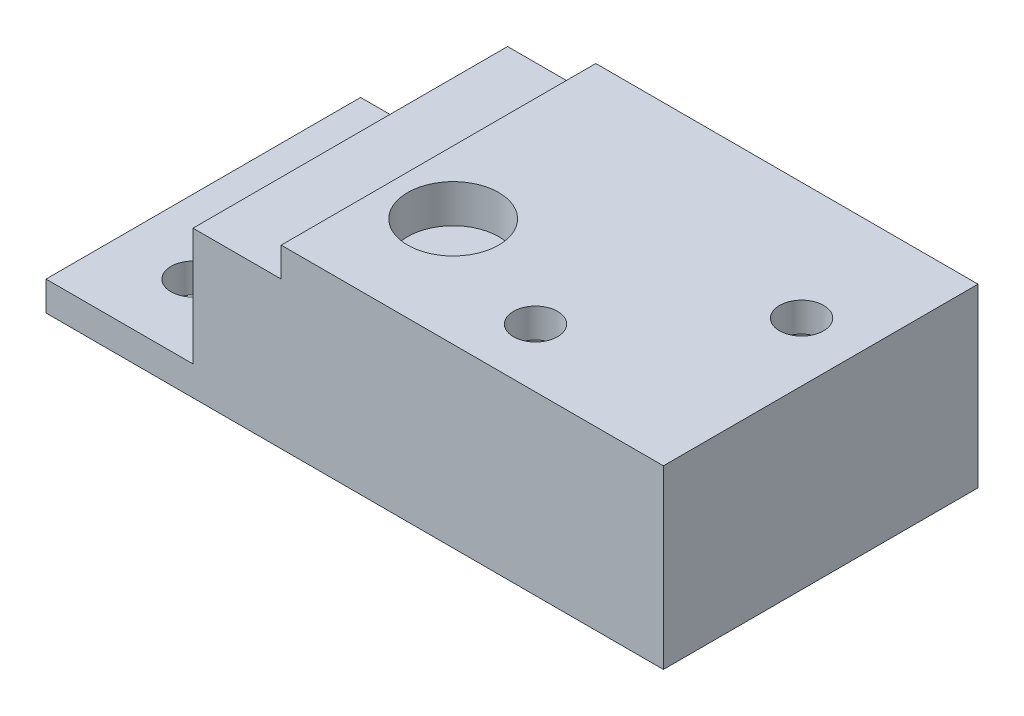
SolidWorks part; units mm, degrees
ref_plane "前视基准面" through (0, 0, 0) normal (0, 0, 1) x (1, 0, 0)
ref_plane "上视基准面" through (0, 0, 0) normal (0, 1, 0) x (1, 0, 0)
ref_plane "右视基准面" through (0, 0, 0) normal (1, 0, 0) x (0, 0, -1)
other "Configuration Table"
sketch "草图1" plane through (0, 0, 0) normal (0, 1, 0) x (1, 0, 0)
  line L33 (0, -21.4) -> (42, -21.4)
  line L34 (0, -21.4) -> (0, 0)
  line L35 (0, 0) -> (42, 0)
  line L36 (42, -21.4) -> (42, 0)
  point P0 (-90.6464, 22.0667)
  dimension "D3" = 21.4
  dimension "D6" = 42
extrude "凸台-拉伸1" add sketch "草图1" along normal blind 12 contours L33 L36 L35 L34 | L33 | L34 region at (21, 0, 10.7)
sketch "草图2" plane through (0, 0, 0) normal (0, 0, -1) x (-1, 0, 0)
  line L0 (0, 12) -> (-42, 12) construction
  line L1 (0, 0) -> (-10, 0)
  line L2 (0, 0) -> (0, 10)
  line L3 (0, 10) -> (-10, 10)
  line L4 (-10, 0) -> (-10, 10)
  line L6 (-10, 0) -> (-16, 0)
  line L7 (-10, 0) -> (-10, 2)
  line L8 (-10, 2) -> (-16, 2)
  line L9 (-16, 0) -> (-16, 2)
  dimension "D1" = 2
  dimension "D2" = 10
  dimension "D3" = 2
  dimension "D4" = 6
extrude "切除-拉伸1" cut sketch "草图2" against normal through all contours L7 L8 L9 L6 | L4 L3 L2 L1
sketch "草图3" plane through (0, 0, 0) normal (0, -1, 0) x (1, 0, 0)
  circle A0 centre (20.3, 14) radius 3.1
  dimension "D1" = 6.2
extrude "切除-拉伸2" cut sketch "草图3" against normal blind 2.6 contours A0
sketch "草图4" plane through (0, 12, 0) normal (0, 1, 0) x (1, 0, 0)
  circle A0 centre (5, -5) radius 2.25
  circle A1 centre (5, -16.4) radius 2.25
  circle A2 centre (29.3, -17.4) radius 2.25
  circle A3 centre (38, -8) radius 2.25
  circle A4 centre (5, -5) radius 1.5
  circle A5 centre (5, -16.4) radius 1.5
  circle A6 centre (38, -8) radius 1.5
  circle A7 centre (29.3, -17.4) radius 1.5
  dimension "D1" = 3
  dimension "D2" = 4.5
extrude "切除-拉伸3" cut sketch "草图4" against normal offset from surface (10 mm away) 2 contours A3 | A2 up to face at (20.3, 0, 10.9)
extrude "切除-拉伸4" cut sketch "草图4<3>" against normal through all contours A4 | A5 | A7 | A6
sketch "草图4<3>" plane through (0, 12, 0) normal (0, 1, 0) x (1, 0, 0) same geometry as "草图4"
ref_plane "基准面1" through (0, -10, 0) normal (0, 1, 0) x (1, 0, 0)
mirror "镜向1" about plane through (0, -10, 0) normal (0, 1, 0) of bodies 189
sketch "草图5" plane through (0, -10, 0) normal (0, 1, 0) x (1, 0, 0)
  line L1 (-21.6188, 8.8444) -> (67.2521, 8.8444)
  line L2 (-21.6188, 8.8444) -> (-21.6188, -33.4141)
  line L3 (-21.6188, -33.4141) -> (67.2521, -33.4141)
  line L4 (67.2521, 8.8444) -> (67.2521, -33.4141)
extrude "切除-拉伸5" cut sketch "草图5" along normal through all
